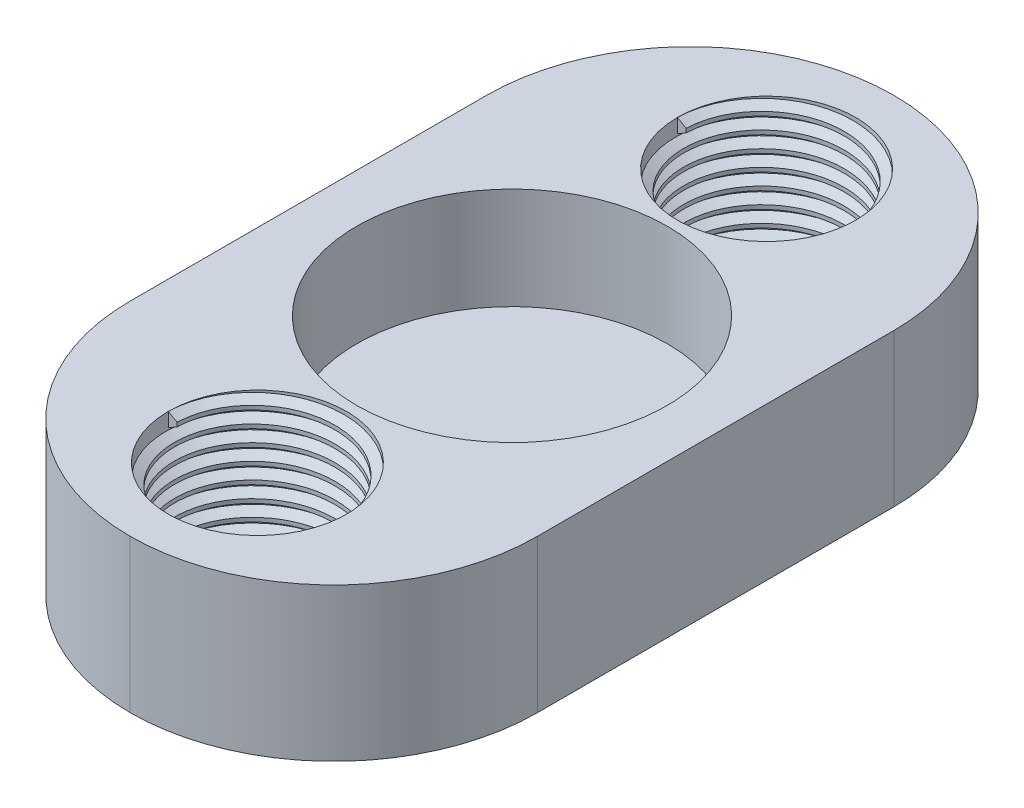
SolidWorks part; units mm, degrees
material "ABS"
ref_plane "Front Plane" through (0, 0, 0) normal (0, 0, 1) x (1, 0, 0)
ref_plane "Top Plane" through (0, 0, 0) normal (0, 1, 0) x (1, 0, 0)
ref_plane "Right Plane" through (0, 0, 0) normal (1, 0, 0) x (0, 0, -1)
sketch "Sketch1" plane through (0, 0, 0) normal (0, 1, 0) x (1, 0, 0)
  line L1 (-4, 7.5) -> (4, 7.5)
  line L2 (-4, 7.5) -> (-4, -7.5)
  line L3 (-4, -7.5) -> (4, -7.5)
  line L4 (4, 7.5) -> (4, -7.5)
  line L5 (-4, 7.5) -> (4, -7.5) construction
  line L6 (-4, -7.5) -> (4, 7.5) construction
  point P0 (0, 0)
  dimension "D1" = 15
  dimension "D2" = 8
extrude "Boss-Extrude1" add sketch "Sketch1" along normal blind 3
sketch "Sketch2" plane through (0, 3, 0) normal (0, 1, 0) x (1, 0, 0)
  line L0 (0, 0) -> (2.248, 0) construction
  circle A1 centre (0, 0) radius 3.05
  point P2 (0, 0)
  dimension "D3" = 6.1
extrude "Cut-Extrude1" cut sketch "Sketch2" against normal blind 2 contours A1
sketch "Sketch3" plane through (0, 3, 0) normal (0, 1, 0) x (1, 0, 0)
  line L0 (-2.6087, 0) -> (2.4028, 0) construction
  circle A0 centre (0, 5) radius 1.75
  circle A1 centre (0, -5) radius 1.75
  point P2 (0, 0)
  dimension "D1" = 3.5
  dimension "D2" = 5
extrude "Cut-Extrude2" cut sketch "Sketch3" against normal through all
thread "Thread1" pitch 0.3175 method extrude profile "Thread Profile1" start angle 0, offset 0, length 0, pitch 0.3175, diameter 3.5
ref_plane "Plane1" through (-1.75, 3, 5) normal (0, 0, 1) x (-1, 0, 0)
sketch "Thread Profile1" plane through (-1.75, 3, 5) normal (0, 0, 1) x (-1, 0, 0)
  line L0 (0, 0) -> (0, 0.3175) construction
  line L11 (0, 0) -> (0, 0.2778)
  line L12 (0, 0.2778) -> (-0.1719, 0.1786)
  line L13 (-0.1719, 0.1786) -> (-0.1719, 0.0992)
  line L15 (-0.1719, 0.0992) -> (0, 0)
  line L17 (-0.1719, 0.1389) -> (0, 0.1389) construction
  point P2 (0, 0)
  dimension "Pitch" = 0.3175
  dimension "Profile_Angle" = 60
  dimension "Profile_Land" = 0.0794
  dimension "Profile_Height" = 0.1719
thread "Thread2" pitch 0.3175 method extrude profile "Thread Profile2" start angle 0, offset 0, length 0, pitch 0.3175, diameter 3.5
ref_plane "Plane2" through (-1.75, 3, -5) normal (0, 0, 1) x (-1, 0, 0)
sketch "Thread Profile2" plane through (-1.75, 3, -5) normal (0, 0, 1) x (-1, 0, 0)
  line L0 (0, 0) -> (0, 0.3175) construction
  line L11 (0, 0) -> (0, 0.2778)
  line L12 (0, 0.2778) -> (-0.1719, 0.1786)
  line L13 (-0.1719, 0.1786) -> (-0.1719, 0.0992)
  line L15 (-0.1719, 0.0992) -> (0, 0)
  line L17 (-0.1719, 0.1389) -> (0, 0.1389) construction
  point P2 (0, 0)
  dimension "Pitch" = 0.3175
  dimension "Profile_Angle" = 60
  dimension "Profile_Land" = 0.0794
  dimension "Profile_Height" = 0.1719
fillet "Fillet1" radius 4 4 edges at (4, 1.5, 7.5) (-4, 1.5, 7.5) (4, 1.5, -7.5) (-4, 1.5, -7.5)
